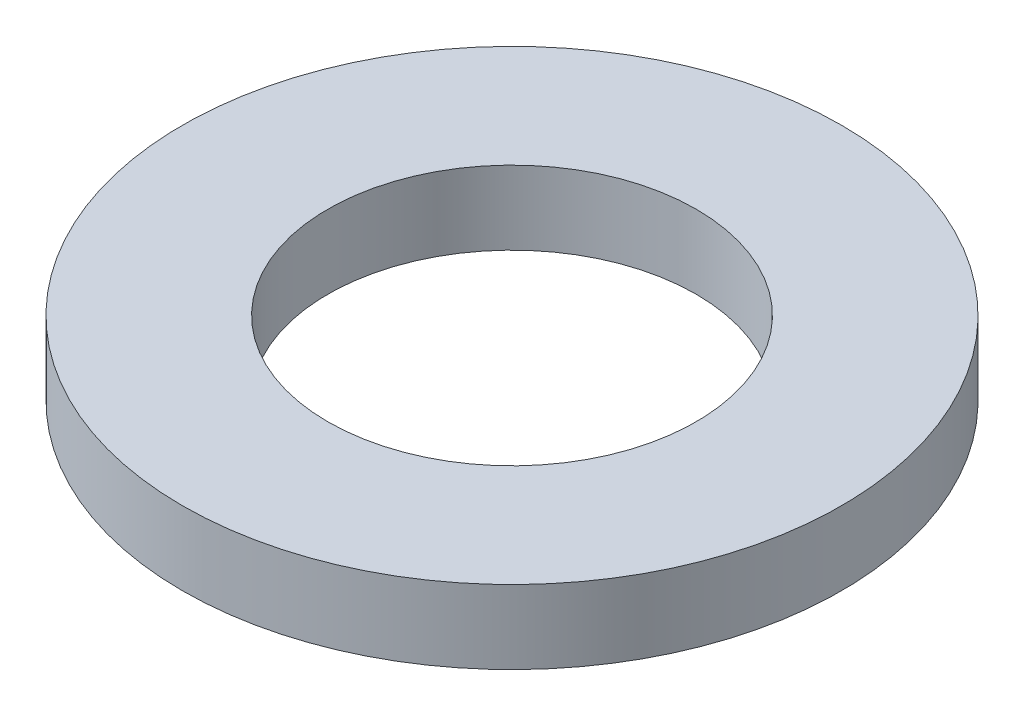
SolidWorks part; units mm, degrees
ref_plane "Front Plane" through (0, 0, 0) normal (0, 0, 1) x (1, 0, 0)
ref_plane "Top Plane" through (0, 0, 0) normal (0, 1, 0) x (1, 0, 0)
ref_plane "Right Plane" through (0, 0, 0) normal (1, 0, 0) x (0, 0, -1)
sketch "Sketch1" plane through (0, 0, 0) normal (0, 1, 0) x (1, 0, 0)
  circle A0 centre (0, 0) radius 85
  dimension "FLANGE_OD" = 170
extrude "Boss-Extrude1" add sketch "Sketch1" along normal blind 19
sketch "Sketch2" plane through (0, 0, 0) normal (0, 1, 0) x (1, 0, 0)
  circle A0 centre (0, 0) radius 47.5
  dimension "BORE_D" = 95
extrude "Cut-Extrude1" cut sketch "Sketch2" along normal through all
sketch "Sketch3" plane through (0, 19, 0) normal (0, 1, 0) x (1, 0, 0)
  circle A0 centre (0, 0) radius 39.4685 construction
  circle A1 centre (-39.4685, 0) radius 2.5324
  dimension "BOLT_D" = 5.0647
  dimension "BOLT_PCD" = 78.9371
extrude "Cut-Extrude2" cut sketch "Sketch3" against normal blind 11.9592 rebuild error yes
pattern_circular "CirPattern1" count 4 over 360 rebuild error yes
